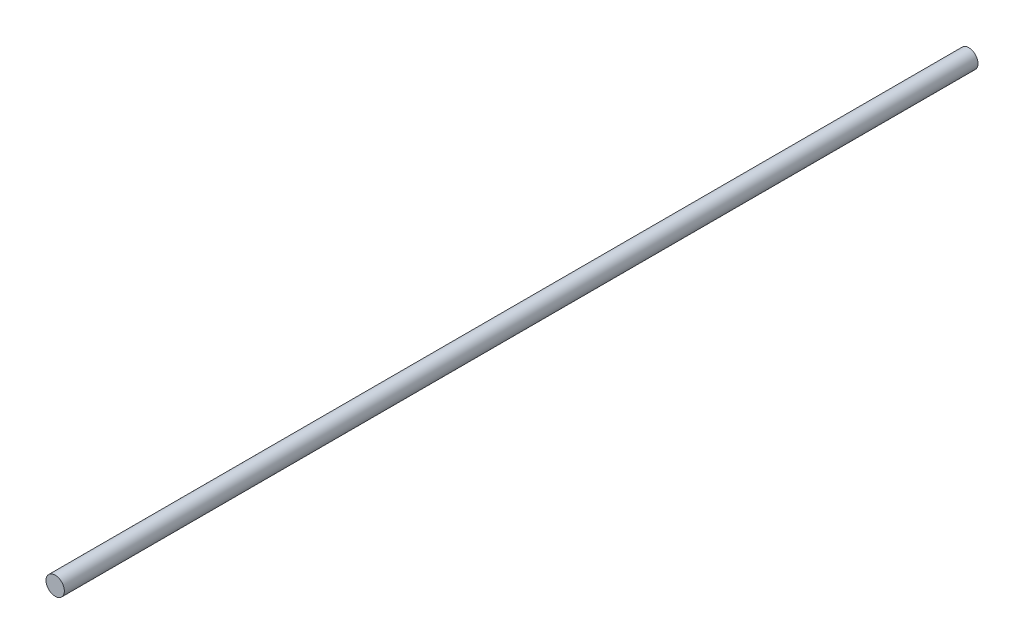
SolidWorks part; units mm, degrees
material "AISI 316 Stainless Steel Sheet (SS)"
ref_plane "Front (1)" through (0, 0, 0) normal (0, 0, 1) x (1, 0, 0)
ref_plane "Top (2)" through (0, 0, 0) normal (0, 1, 0) x (1, 0, 0)
ref_plane "Right (3)" through (0, 0, 0) normal (1, 0, 0) x (0, 0, -1)
ref_axis "X Axis" through (13.5064, 0, 0) along (-1, 0, 0)
ref_axis "Y Axis" through (0, 12.3593, 0) along (0, -1, 0)
ref_axis "Z Axis" through (0, 0, 14.1119) along (0, 0, -1)
sketch "Sketch2" plane through (0, 0, 0) normal (1, 0, 0) x (0, 0, -1)
  line L0 (-7.8, 0) -> (0, 0) construction
  line L1 (-7.8, 0) -> (390.0032, 0)
  line L2 (-7.8, 0) -> (-7.8, 4)
  line L3 (-7.8, 4) -> (390.0032, 4)
  line L4 (390.0032, 0) -> (390.0032, 4)
  dimension "D1" = 8
  dimension "D2" = 397.8032
revolve "Revolve1" add sketch "Sketch2" angle 360 about L0
